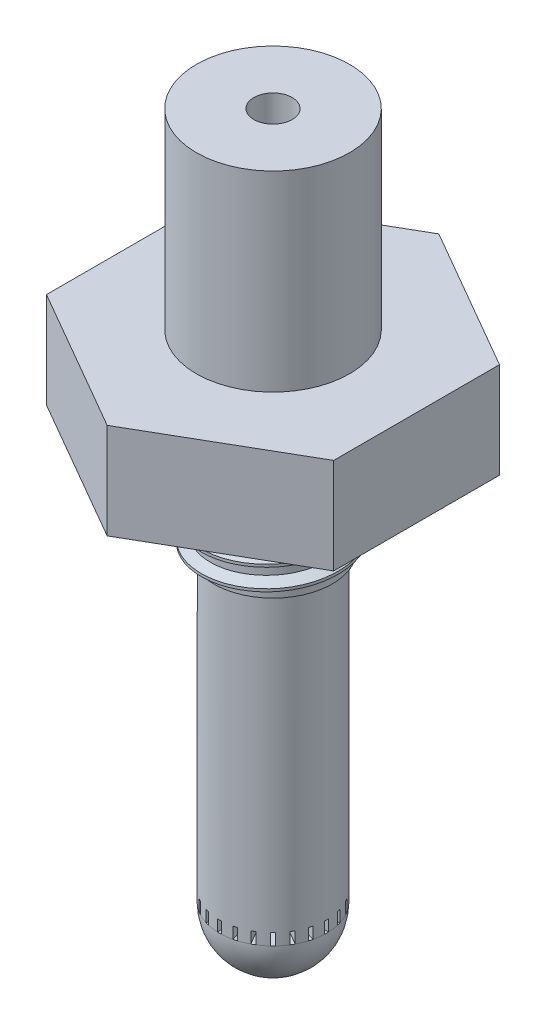
SolidWorks part; units mm, degrees
ref_plane "Front Plane" through (0, 0, 0) normal (0, 0, 1) x (1, 0, 0)
ref_plane "Top Plane" through (0, 0, 0) normal (0, 1, 0) x (1, 0, 0)
ref_plane "Right Plane" through (0, 0, 0) normal (1, 0, 0) x (0, 0, -1)
sketch "Sketch1" plane through (0, 0, 0) normal (0, 0, 1) x (1, 0, 0)
  line L0 (-3.556, -2.0672) -> (-1.27, -2.0672) construction
  line L1 (0, 8.2157) -> (0, -2.0672) construction
  line L2 (-3.556, 18.1817) -> (-1.27, 18.1817)
  line L3 (-3.556, -2.0672) -> (-3.556, 18.1817)
  line L5 (0, -1.6066) -> (0, -5.6232)
  line L7 (-1.27, 18.1817) -> (-1.27, -2.0672)
  arc A0 (-1.27, -2.0672) -> (0, -1.6066) centre (-1.3754, 0.2045) ccw
  arc A2 (-3.556, -2.0672) -> (0, -5.6232) centre (0, -2.0672) ccw
  dimension "D4" = 20.2489
  dimension "D1" = 3.556
  dimension "D2" = 3.556
  dimension "D3" = 1.27
revolve "Revolve2" add sketch "Sketch1" angle 360 about L1
ref_plane "Plane1" through (-3.556, 0, 0) normal (-1, 0, 0) x (0, 0, 1)
sketch "Sketch2" plane through (-3.556, 0, 0) normal (-1, 0, 0) x (0, 0, 1)
  line L0 (0.127, -2.0672) -> (-0.127, -2.0672)
  line L1 (-0.127, -2.0672) -> (-0.127, -1.3052)
  line L2 (-0.127, -1.3052) -> (0.127, -1.3052)
  line L3 (0.127, -1.3052) -> (0.127, -2.0672)
  dimension "D1" = 0.762
  dimension "D2" = 0.254
extrude "Cut-Extrude1" cut sketch "Sketch2" along normal up to surface (2.2924 mm away)
pattern_circular "CirPattern1" count 24 over 360 about axis through (0, 0, 0) along (0, 1, 0) of "Cut-Extrude1"
ref_plane "Plane2" through (0, 18.1817, 0) normal (0, -1, 0) x (-1, 0, 0)
sketch "Sketch3" plane through (0, 18.1817, 0) normal (0, -1, 0) x (-1, 0, 0)
  circle A0 centre (0, 0) radius 3.937
  circle A1 centre (0, 0) radius 1.27
extrude "Boss-Extrude1" add sketch "Sketch3" against normal blind 6.2916
ref_plane "Plane3" through (0, 24.4732, 0) normal (0, 1, 0) x (1, 0, 0)
sketch "Sketch4" plane through (0, 24.4732, 0) normal (0, 1, 0) x (1, 0, 0)
  line L0 (0, -55) -> (0, 55) construction
  line L1 (-9.525, 5.4993) -> (-9.525, -5.4993)
  line L2 (-9.525, -5.4993) -> (0, -10.9985)
  line L3 (0, -10.9985) -> (9.525, -5.4993)
  line L4 (9.525, -5.4993) -> (9.525, 5.4993)
  line L5 (9.525, 5.4993) -> (0, 10.9985)
  line L6 (0, 10.9985) -> (-9.525, 5.4993)
  circle A0 centre (0, 0) radius 9.525 construction
  circle A1 centre (0, 0) radius 1.27
  dimension "D1" = 19.05
extrude "Boss-Extrude2" add sketch "Sketch4" along normal blind 6.35
sketch "Sketch5" plane through (0, 24.4732, 0) normal (0, -1, 0) x (1, 0, 0)
  circle A0 centre (0, 0) radius 7.62 construction
  circle A1 centre (0, 0) radius 7.874
  circle A2 centre (0, 0) radius 7.366
  dimension "D1" = 0.254
  dimension "D3" = 15.24
  dimension "D2" = 0.254
sketch "Sketch6" plane through (0, 30.8232, 0) normal (0, 1, 0) x (1, 0, 0)
  circle A0 centre (0, 0) radius 5.08
  circle A2 centre (0, 0) radius 1.27
extrude "Boss-Extrude3" add sketch "Sketch6" along normal blind 12.7
sketch "Sketch7" plane through (0, 18.1817, 0) normal (0, -1, 0) x (-1, 0, 0)
  circle A0 centre (0, 0) radius 4.0005
  dimension "D1" = 8.001
sketch "Sketch8" plane through (0, 0, 0) normal (1, 0, 0) x (0, 0, -1)
  line L0 (3.937, 17.7452) -> (3.937, 18.6181)
  line L1 (3.937, 18.6181) -> (4.5402, 18.2698)
  line L2 (4.5402, 18.2698) -> (4.5402, 18.0935)
  line L3 (4.5402, 18.0935) -> (3.937, 17.7452)
  line L4 (3.937, 18.1817) -> (4.5402, 18.1817) construction
  line L5 (3.937, 18.1817) -> (3.937, 19.5186) construction
  line L6 (3.5743, 18.1817) -> (4.3786, 18.1817) construction
  dimension "D1" = 60
  dimension "D2" = 0.1764
  dimension "D3" = 0.6032
curve "Helix/Spiral1" pitch 1.4111 height 7.0556 turns 5
sweep "Sweep1" add profiles "Sketch8" path "Helix/Spiral1"
sketch "Sketch9" plane through (0, 0, 0) normal (1, 0, 0) x (0, 0, -1)
  line L1 (3.7695, 18.1817) -> (8.7987, 18.1817)
  line L2 (3.7695, 18.1817) -> (3.7695, 16.7479)
  line L3 (3.7695, 16.7479) -> (8.7987, 16.7479)
  line L4 (8.7987, 18.1817) -> (8.7987, 16.7479)
  line L5 (0, 0) -> (0, 12.757) construction
  line L6 (0.4564, 24.4732) -> (3.937, 24.4732) construction
  dimension "D1" = 6.2916
  dimension "D2" = 5.0291
  dimension "D3" = 1.4338
  dimension "D4" = 3.7695
revolve "Cut-Revolve2" cut sketch "Sketch9" angle 360 about L5
